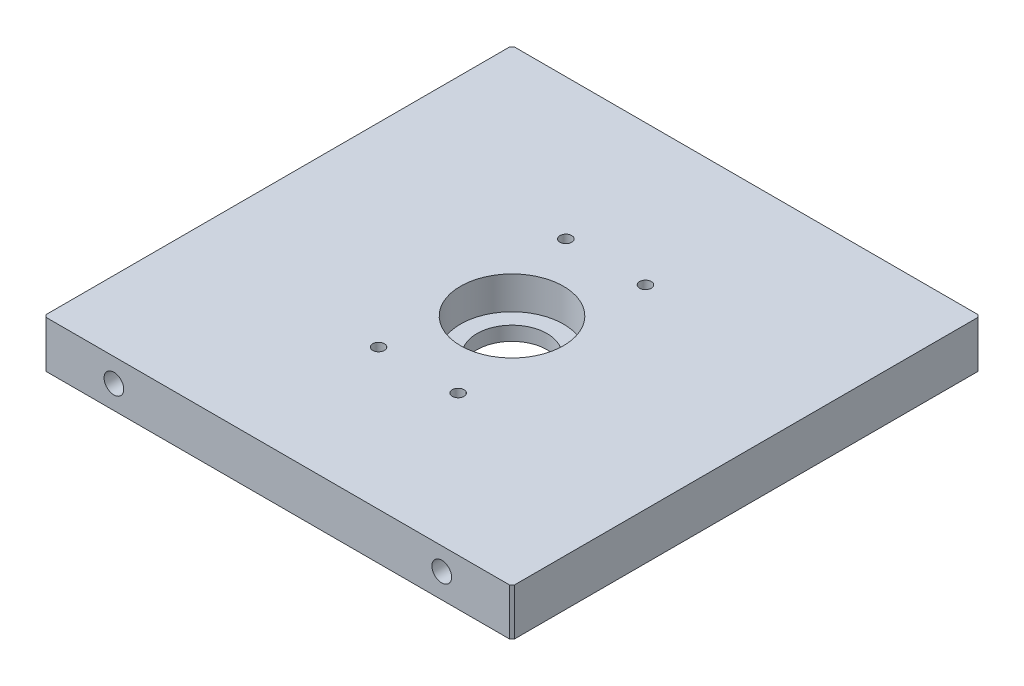
SolidWorks part; units mm, degrees
material "6061 Alloy"
ref_plane "Front Plane" through (0, 0, 0) normal (0, 0, 1) x (1, 0, 0)
ref_plane "Top Plane" through (0, 0, 0) normal (0, 1, 0) x (1, 0, 0)
ref_plane "Right Plane" through (0, 0, 0) normal (1, 0, 0) x (0, 0, -1)
sketch "Sketch1" plane through (0, 0, 0) normal (0, 1, 0) x (1, 0, 0)
  line L1 (-50, 50) -> (50, 50)
  line L2 (-50, 50) -> (-50, -50)
  line L3 (-50, -50) -> (50, -50)
  line L4 (50, 50) -> (50, -50)
  circle A0 centre (0, 0) radius 7.5
  dimension "D3" = 100
  dimension "D4" = 15
  dimension "D1" = 50
  dimension "D2" = 50
extrude "Boss-Extrude1" add sketch "Sketch1" along normal blind 5 and the other way blind 5
sketch "Sketch2" plane through (0, 5, 0) normal (0, 1, 0) x (1, 0, 0)
  circle A0 centre (0, 0) radius 11
  dimension "D1" = 22
extrude "Cut-Extrude1" cut sketch "Sketch2" against normal blind 7
hole_wizard "Tap Drill for M5x0.8 Tap1" positions "Sketch5" profile "Sketch6" hole size "M5x0.8" standard "ANSI Metric"
sketch "Sketch5" plane through (0, 0, 50) normal (0, 0, 1) x (1, 0, 0)
  line L0 (-50, -5) -> (-50, 5) construction
  line L1 (50, -5) -> (50, 5) construction
  line L2 (-50, 5) -> (50, 5) construction
  point P0 (-35, 0)
  point P2 (35, 0.2375)
  dimension "D1" = 15
  dimension "D2" = 15
  dimension "D3" = 4.7625
sketch "Sketch6" plane through (-35, 0, 50) normal (1, 0, 0) x (0, -1, 0)
  line L0 (0, 0) -> (0, 11.2618)
  line L1 (0, 11.2618) -> (2.1, 10)
  line L2 (2.1, 10) -> (2.1, 0)
  line L5 (2.1, 0) -> (0, 0)
  line L10 (0, 11.2618) -> (-2.1, 10) construction
  line L11 (0, -6.35) -> (0, 107.95) construction
  dimension "Hole Dia." = 4.2
  dimension "Hole Depth" = 10
  dimension "Drill Angle" = 118
ref_plane "Plane1" through (0, 0, 0) normal (0, 0, -1) x (-1, 0, 0)
mirror "Mirror1" about plane through (0, 0, 0) normal (0, 0, -1) of "Tap Drill for M5x0.8 Tap1"
hole_wizard "Tap Drill for M3x0.5 Tap2" positions "Sketch11" profile "Sketch12" hole size "M3x0.5" standard "ANSI Metric"
sketch "Sketch11" plane through (0, 5, 0) normal (0, 1, 0) x (1, 0, 0)
  line L0 (0, 23.6539) -> (0, -21.2998) construction
  line L3 (5.5, 0) -> (-5.5, 0) construction
  point P0 (-8.5, -20)
  point P2 (8.5, -20)
  point P4 (8.5, 20)
  point P6 (-8.5, 20)
  dimension "D1" = 8.5
  dimension "D2" = 8.5
  dimension "D3" = 20
  dimension "D4" = 20
  dimension "D5" = 8.5
  dimension "D6" = 8.5
  dimension "D7" = 20
  dimension "D8" = 20
sketch "Sketch12" plane through (-8.5, 5, 20) normal (1, 0, 0) x (0, 0, 1)
  line L0 (0, 0) -> (0, 6.7511)
  line L1 (0, 6.7511) -> (1.25, 6)
  line L2 (1.25, 6) -> (1.25, 0)
  line L5 (1.25, 0) -> (0, 0)
  line L10 (0, 6.7511) -> (-1.25, 6) construction
  line L11 (0, -6.35) -> (0, 107.95) construction
  dimension "Hole Dia." = 2.5
  dimension "Hole Depth" = 6
  dimension "Drill Angle" = 118
chamfer "Chamfer1" distance 0.5 angle 45 4 edges at (-50, 0, -50) (-50, 0, 50) (50, 0, 50) (50, 0, -50)
